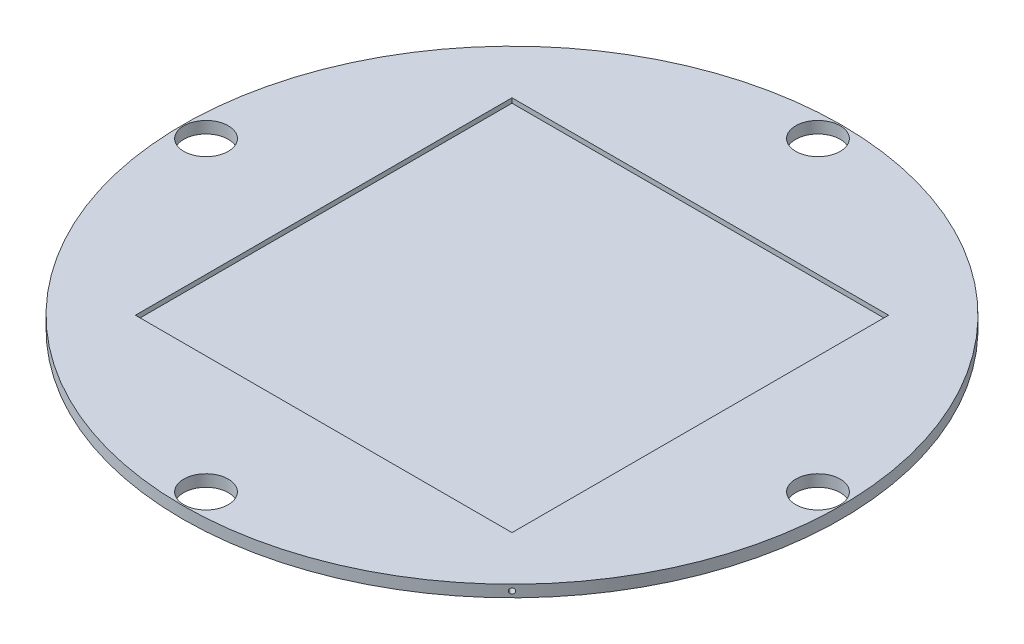
SolidWorks part; units mm, degrees
ref_plane "Front Plane" through (0, 0, 0) normal (0, 0, 1) x (1, 0, 0)
ref_plane "Top Plane" through (0, 0, 0) normal (0, 1, 0) x (1, 0, 0)
ref_plane "Right Plane" through (0, 0, 0) normal (1, 0, 0) x (0, 0, -1)
sketch "Sketch1" plane through (0, 0, 0) normal (0, 1, 0) x (1, 0, 0)
  circle A0 centre (0, 0) radius 88.9
  dimension "D1" = 177.8
extrude "Boss-Extrude1" add sketch "Sketch1" along normal blind 3.175
sketch "Sketch2" plane through (0, 3.175, 0) normal (0, 1, 0) x (1, 0, 0)
  circle A0 centre (0, 82.55) radius 5.9944
  dimension "D1" = 11.9888
  dimension "D2" = 82.55
extrude "Cut-Extrude1" cut sketch "Sketch2" against normal through all
pattern_circular "CirPattern1" count 4 over 360 about axis through (0, 3.175, 0) along (0, 1, 0) of "Cut-Extrude1"
ref_plane "Plane1" through (-62.8618, 0, 62.8618) normal (-0.7071, 0, 0.7071) x (0, -1, 0)
sketch "Sketch3" plane through (-62.8618, 0, 62.8618) normal (-0.7071, 0, 0.7071) x (0, -1, 0)
  line L0 (0, 0) -> (-3.1494, 0) construction
  circle A0 centre (-1.5875, 0) radius 0.6985
  dimension "D1" = 1.397
  dimension "D2" = 1.5875
extrude "Cut-Extrude2" cut sketch "Sketch3" against normal blind 3.175
pattern_circular "CirPattern2" count 4 over 360 about axis through (0, 3.175, 0) along (0, 1, 0) of "Cut-Extrude2"
sketch "Sketch4" plane through (0, 3.175, 0) normal (0, 1, 0) x (1, 0, 0)
  line L1 (-50.8, -50.8) -> (50.8, -50.8)
  line L2 (-50.8, -50.8) -> (-50.8, 50.8)
  line L3 (-50.8, 50.8) -> (50.8, 50.8)
  line L4 (50.8, -50.8) -> (50.8, 50.8)
  line L5 (-50.8, -50.8) -> (50.8, 50.8) construction
  line L6 (-50.8, 50.8) -> (50.8, -50.8) construction
  point P0 (0, 0)
  dimension "D1" = 101.6
  dimension "D2" = 101.6
extrude "Cut-Extrude3" cut sketch "Sketch4" against normal blind 1.27
